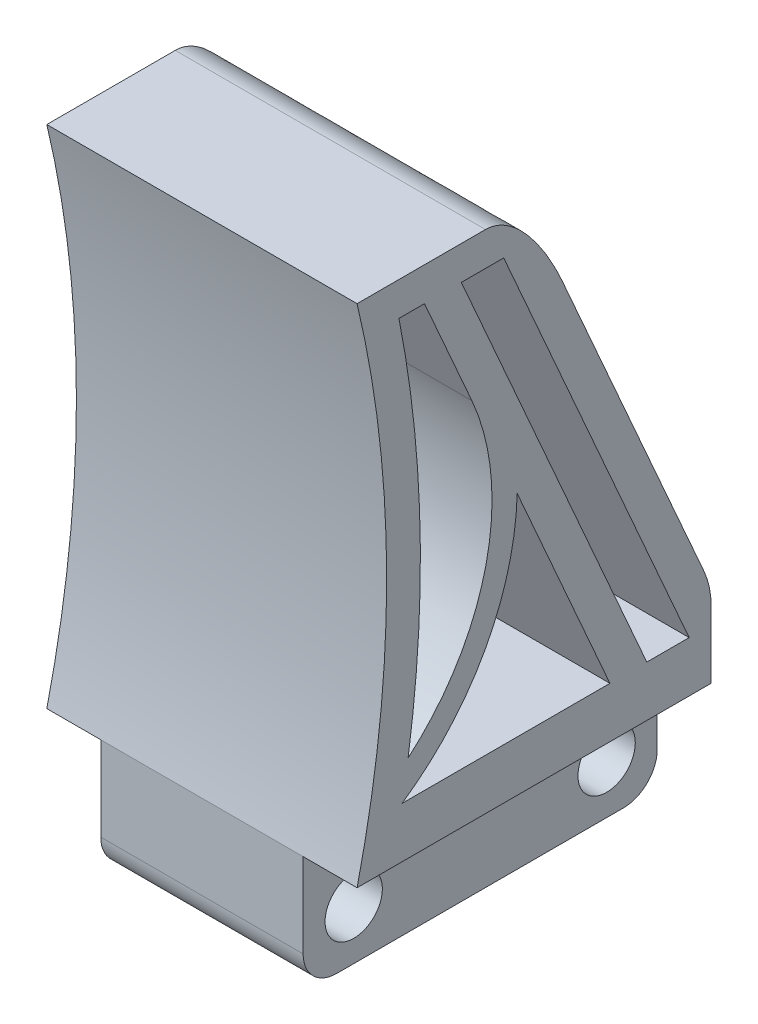
SolidWorks part; units mm, degrees
ref_plane "Front Plane" through (0, 0, 0) normal (0, 0, 1) x (1, 0, 0)
ref_plane "Top Plane" through (0, 0, 0) normal (0, 1, 0) x (1, 0, 0)
ref_plane "Right Plane" through (0, 0, 0) normal (1, 0, 0) x (0, 0, -1)
sketch "Sketch1" plane through (0, 0, 0) normal (1, 0, 0) x (0, 0, -1)
  line L0 (0, 0) -> (21, 0)
  line L4 (10, 30) -> (0, 30)
  line L5 (21, 0) -> (21, 5)
  line L6 (21, 5) -> (10, 30)
  line L7 (8.695, 28) -> (19.695, 3)
  line L9 (17.1822, 3) -> (6.1822, 28)
  line L11 (8.695, 28) -> (6.1822, 28)
  line L12 (17.1822, 3) -> (19.695, 3)
  line L13 (3.9971, 28) -> (14.9971, 3)
  line L14 (14.9971, 3) -> (2.6711, 3)
  line L15 (3.9971, 28) -> (2.4812, 28)
  arc A0 (0, 30) -> (0, 0) centre (-63.2456, 15) cw
  arc A2 (2.4812, 28) -> (2.6711, 3) centre (-63.2456, 15) cw
  arc A3 (6.8055, 21.6173) -> (3.0273, 5.1556) centre (-6.1358, 15.9231) cw
  arc A4 (9.4971, 15.5) -> (2.6711, 3) centre (-6.1358, 15.9231) cw
  point P26 (9.4971, 15.5)
  dimension "D4" = 5
  dimension "D5" = 65
  dimension "D10" = 2
  dimension "D11" = 2
  dimension "D12" = 1.5
  dimension "D1" = 21
  dimension "D2" = 30
  dimension "D3" = 10
  dimension "D6" = 2.3
  dimension "D7" = 2
  dimension "D8" = 3
  dimension "D9" = 2
extrude "Boss-Extrude1" add sketch "Sketch1" along normal blind 18.4 contours L4 A0 L0 L5 L6 A2 L15 L13 L14 L12 L9 L11 L7 | A4 L13 A3 A2 region at (0, 15, -2.1206) region at (0, 10.3649, -6.9081)
fillet "Fillet1" radius 7 1 edges at (9.2, 30, -10) second distance 5 first distance on face at (9.2, 17.5, -15.5)
fillet "Fillet2" radius 5 1 edges at (9.2, 5, -21)
sketch "Sketch2" plane through (0, 0, 0) normal (0, -1, 0) x (-1, 0, 0)
  line L6 (-18.4, 0) -> (0, 0) construction
  line L7 (-3.2, 0) -> (-15.2, 0)
  line L8 (-3.2, 0) -> (-3.2, 21)
  line L9 (-3.2, 21) -> (-15.2, 21)
  line L10 (-15.2, 0) -> (-15.2, 21)
  line L11 (-18.4, 21) -> (0, 21) construction
  point P8 (-9.2, 21)
  point P9 (-9.2, 21)
  dimension "D1" = 12
extrude "Boss-Extrude2" add sketch "Sketch2" along normal blind 7
sketch "Sketch3" plane through (15.2, 0, 0) normal (1, 0, 0) x (0, 0, -1)
  line L0 (21, -7) -> (0, -7) construction
  line L1 (3, -4) -> (18, -4) construction
  circle A0 centre (3, -4) radius 1.7
  circle A1 centre (18, -4) radius 1.7
  point P4 (10.5, -7)
  point P7 (10.5, -4)
  dimension "D1" = 15
  dimension "D2" = 3
  dimension "D3" = 3.4
extrude "Cut-Extrude1" cut sketch "Sketch3" against normal through all
fillet "Fillet3" radius 2 2 edges at (9.2, -7, 0) (9.2, -7, -21)
